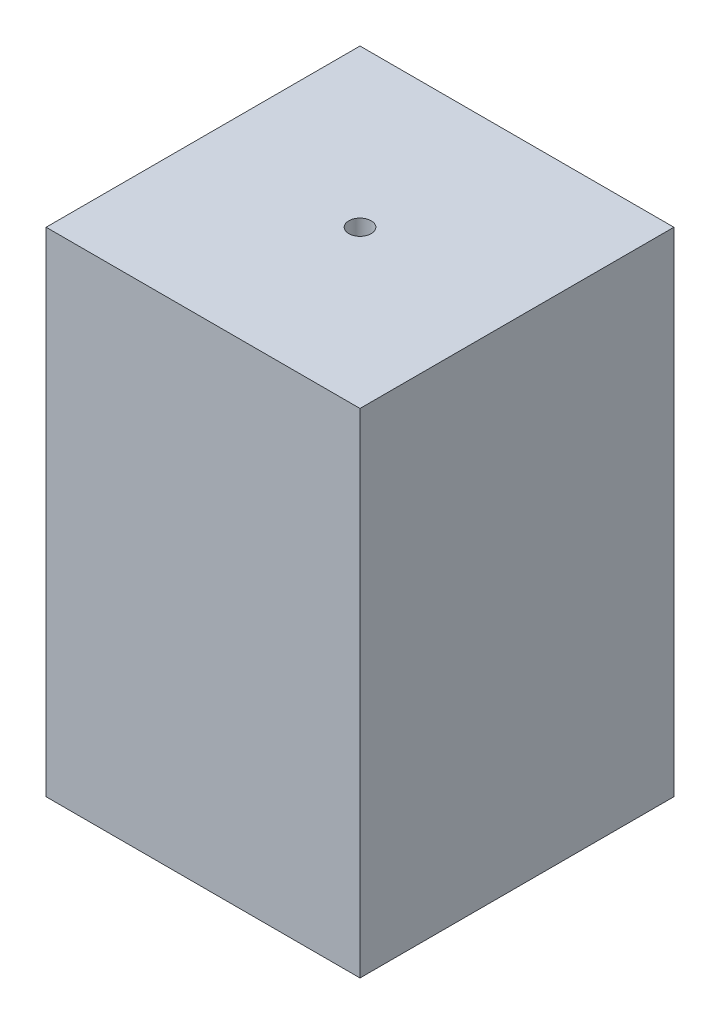
SolidWorks part; units mm, degrees
ref_plane "Front Plane" through (0, 0, 0) normal (0, 0, 1) x (1, 0, 0)
ref_plane "Top Plane" through (0, 0, 0) normal (0, 1, 0) x (1, 0, 0)
ref_plane "Right Plane" through (0, 0, 0) normal (1, 0, 0) x (0, 0, -1)
sketch "Sketch1" plane through (0, 0, 0) normal (0, 1, 0) x (1, 0, 0)
  line L1 (-70, 70) -> (70, 70)
  line L2 (-70, 70) -> (-70, -70)
  line L3 (-70, -70) -> (70, -70)
  line L4 (70, 70) -> (70, -70)
  line L5 (-70, 70) -> (70, -70) construction
  line L6 (-70, -70) -> (70, 70) construction
  circle A0 centre (0, 0) radius 5
  point P0 (0, 0)
extrude "Boss-Extrude1" add sketch "Sketch1" along normal blind 10
sketch "Sketch3" plane through (0, 0, 0) normal (0, -1, 0) x (1, 0, 0)
  line L1 (60, -60) -> (-60, -60)
  line L2 (60, -60) -> (60, 60)
  line L3 (60, 60) -> (-60, 60)
  line L4 (-60, -60) -> (-60, 60)
  line L5 (60, -60) -> (-60, 60) construction
  line L6 (60, 60) -> (-60, -60) construction
  line L7 (70, -70) -> (-70, -70)
  line L8 (70, -70) -> (70, 70)
  line L9 (70, 70) -> (-70, 70)
  line L10 (-70, -70) -> (-70, 70)
  line L11 (70, -70) -> (-70, 70) construction
  line L12 (70, 70) -> (-70, -70) construction
  point P0 (0, 0)
  point P6 (0, 0)
extrude "Boss-Extrude2" add sketch "Sketch3" along normal blind 210
